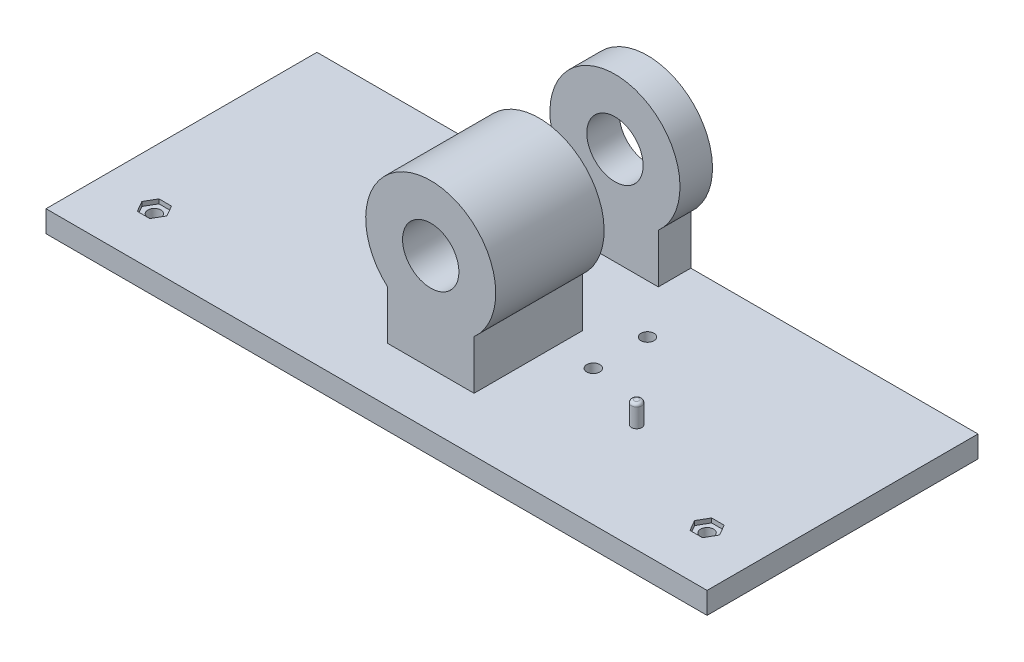
SolidWorks part; units mm, degrees
ref_plane "Front Plane" through (0, 0, 0) normal (0, 0, 1) x (1, 0, 0)
ref_plane "Top Plane" through (0, 0, 0) normal (0, 1, 0) x (1, 0, 0)
ref_plane "Right Plane" through (0, 0, 0) normal (1, 0, 0) x (0, 0, -1)
sketch "Sketch1" plane through (0, 0, 0) normal (0, 1, 0) x (1, 0, 0)
  line L0 (152.5, 125) -> (152.5, 0) construction
  line L1 (0, 0) -> (305, 0)
  line L2 (0, 0) -> (0, 125)
  line L3 (0, 125) -> (305, 125)
  line L4 (305, 0) -> (305, 125)
  line L5 (25, 100) -> (280, 100) construction
  line L6 (280, 25) -> (280, 100) construction
  line L7 (25, 25) -> (280, 25) construction
  line L8 (25, 25) -> (25, 100) construction
  line L9 (152.5, 62.5) -> (25, 62.5) construction
  line L10 (30.7735, 100) -> (27.8868, 105) construction
  line L11 (27.8868, 105) -> (22.1132, 105) construction
  line L12 (22.1132, 105) -> (19.2265, 100) construction
  line L13 (19.2265, 100) -> (22.1132, 95) construction
  line L14 (22.1132, 95) -> (27.8868, 95) construction
  line L15 (27.8868, 95) -> (30.7735, 100) construction
  line L16 (27.8868, 30) -> (30.7735, 25) construction
  line L17 (22.1132, 30) -> (27.8868, 30) construction
  line L18 (19.2265, 25) -> (22.1132, 30) construction
  line L19 (22.1132, 20) -> (19.2265, 25) construction
  line L20 (27.8868, 20) -> (22.1132, 20) construction
  line L21 (30.7735, 25) -> (27.8868, 20) construction
  line L22 (282.8868, 30) -> (277.1132, 30) construction
  line L23 (285.7735, 25) -> (282.8868, 30) construction
  line L24 (282.8868, 20) -> (285.7735, 25) construction
  line L25 (277.1132, 20) -> (282.8868, 20) construction
  line L26 (274.2265, 25) -> (277.1132, 20) construction
  line L27 (277.1132, 30) -> (274.2265, 25) construction
  line L28 (277.1132, 95) -> (274.2265, 100) construction
  line L29 (282.8868, 95) -> (277.1132, 95) construction
  line L30 (285.7735, 100) -> (282.8868, 95) construction
  line L31 (282.8868, 105) -> (285.7735, 100) construction
  line L32 (277.1132, 105) -> (282.8868, 105) construction
  line L33 (274.2265, 100) -> (277.1132, 105) construction
  line L34 (172.5, 75) -> (172.5, 125) construction
  line L35 (132.5, 0) -> (172.5, 0) construction
  line L36 (132.5, 0) -> (132.5, 125) construction
  line L37 (132.5, 125) -> (172.5, 125) construction
  line L38 (172.5, 0) -> (172.5, 125) construction
  line L39 (132.5, 75) -> (172.5, 75) construction
  line L40 (132.5, 75) -> (132.5, 25) construction
  line L41 (132.5, 25) -> (172.5, 25) construction
  line L42 (172.5, 75) -> (172.5, 25) construction
  line L43 (172.5, 75) -> (190, 62.5) construction
  line L48 (190, 62.5) -> (190, 75) construction
  line L49 (190, 75) -> (172.5, 75) construction
  line L50 (190, 62.5) -> (190, 75) construction
  line L51 (190, 75) -> (190, 87.5) construction
  circle A1 centre (25, 100) radius 5 construction
  circle A3 centre (280, 25) radius 3
  circle A4 centre (25, 25) radius 3
  circle A5 centre (190, 62.5) radius 3
  circle A7 centre (190, 87.5) radius 3
  dimension "D3" = 6
  dimension "D7" = 6
  dimension "D1" = 305
  dimension "D2" = 125
  dimension "D5" = 10
  dimension "D6" = 40
  dimension "D8" = 50
  dimension "D9" = 12.5
  dimension "D10" = 17.5
  dimension "D4" = 25
  dimension "D11" = 2
extrude "Boss-Extrude1" add sketch "Sketch1" along normal blind 10
sketch "Sketch6" plane through (0, 10, 0) normal (0, 1, 0) x (1, 0, 0)
  line L0 (152.5, 125) -> (152.5, 0) construction
  line L7 (305, 125) -> (0, 125) construction
  line L8 (0, 0) -> (305, 0) construction
  line L9 (152.5, 62.5) -> (0, 62.5) construction
  line L10 (0, 125) -> (0, 0) construction
  line L29 (27.8868, 30) -> (30.7735, 25)
  line L30 (274.2265, 25) -> (277.1132, 20)
  line L31 (277.1132, 20) -> (282.8868, 20)
  line L32 (282.8868, 20) -> (285.7735, 25)
  line L33 (285.7735, 25) -> (282.8868, 30)
  line L34 (282.8868, 30) -> (277.1132, 30)
  line L35 (277.1132, 30) -> (274.2265, 25)
  line L36 (22.1132, 30) -> (27.8868, 30)
  line L37 (19.2265, 25) -> (22.1132, 30)
  line L38 (22.1132, 20) -> (19.2265, 25)
  line L39 (27.8868, 20) -> (22.1132, 20)
  line L40 (30.7735, 25) -> (27.8868, 20)
  circle A0 centre (280, 25) radius 5 construction
  dimension "D1" = 10
extrude "Cut-Extrude1" cut sketch "Sketch6" against normal blind 2
sketch "Sketch7" plane through (0, 10, 0) normal (0, 1, 0) x (1, 0, 0)
  line L0 (0, 0) -> (305, 0) construction
  line L1 (132.5, 25) -> (172.5, 25)
  line L2 (132.5, 25) -> (132.5, 75)
  line L3 (132.5, 75) -> (172.5, 75)
  line L4 (172.5, 25) -> (172.5, 75)
  line L5 (152.5, 0) -> (152.5, 125) construction
  line L6 (305, 125) -> (0, 125) construction
  line L7 (172.5, 75) -> (172.5, 125) construction
  line L18 (132.5, 110) -> (172.5, 110)
  line L19 (132.5, 110) -> (132.5, 125)
  line L20 (132.5, 125) -> (172.5, 125)
  line L21 (172.5, 110) -> (172.5, 125)
  point P11 (152.5, 75)
  point P20 (152.5, 110)
  dimension "D1" = 40
  dimension "D4" = 15
extrude "Boss-Extrude2" add sketch "Sketch7" along normal blind 22.6393
sketch "Sketch11" plane through (0, 0, -25) normal (0, 0, 1) x (1, 0, 0)
  circle A0 centre (152.5, 55) radius 30
  circle A1 centre (152.5, 55) radius 13
  dimension "D1" = 60
  dimension "D2" = 26
extrude "Boss-Extrude3" add sketch "Sketch11" against normal up to surface (100 mm away) up to face at (152.5, 13.1598, -125)
ref_plane "Plane1" through (0, 0, -62.5) normal (0, 0, 1) x (1, 0, 0)
sketch "Sketch12" plane through (305, 0, 0) normal (1, 0, 0) x (0, 0, -1)
  line L0 (125, 85) -> (25, 85) construction
  line L1 (75, 10) -> (110, 10)
  line L2 (75, 10) -> (75, 85)
  line L3 (75, 85) -> (110, 85)
  line L4 (110, 10) -> (110, 85)
  line L6 (110, 32.6393) -> (110, 10) construction
extrude "Cut-Extrude2" cut sketch "Sketch12" against normal through all
sketch "Sketch13" plane through (0, 10, 0) normal (0, 1, 0) x (1, 0, 0)
  line L0 (222.5, 50) -> (172.5, 50) construction
  line L1 (172.5, 25) -> (172.5, 75) construction
  circle A1 centre (222.5, 50) radius 2.4
  dimension "D1" = 4.8
  dimension "D2" = 50
extrude "Boss-Extrude4" add sketch "Sketch13" along normal blind 10
sketch "Sketch14" plane through (0, 0, 0) normal (0, -1, 0) x (1, 0, 0)
  line L0 (195.7735, -87.5) -> (192.8868, -82.5)
  line L1 (195.7735, -62.5) -> (192.8868, -57.5)
  line L2 (192.8868, -57.5) -> (187.1132, -57.5)
  line L3 (187.1132, -57.5) -> (184.2265, -62.5)
  line L4 (184.2265, -62.5) -> (187.1132, -67.5)
  line L5 (187.1132, -67.5) -> (192.8868, -67.5)
  line L6 (192.8868, -67.5) -> (195.7735, -62.5)
  line L7 (192.8868, -82.5) -> (187.1132, -82.5)
  line L8 (187.1132, -82.5) -> (184.2265, -87.5)
  line L9 (184.2265, -87.5) -> (187.1132, -92.5)
  line L10 (187.1132, -92.5) -> (192.8868, -92.5)
  line L11 (192.8868, -92.5) -> (195.7735, -87.5)
  circle A0 centre (190, -62.5) radius 5 construction
  dimension "D1" = 10
  dimension "D3" = 15
  dimension "D2" = 2
extrude "Cut-Extrude3" cut sketch "Sketch14" against normal blind 4
fillet "Fillet1" radius 1.3 1 edges at (222.5, 20, -47.6)
equation "\"joint_width\"=4"
equation "\"D2@Sketch7\"=5"
equation "\"short_base_length\"=12.5"
equation "\"D2@Sketch1\"=\"short_base_length\""
equation "\"outer_diam_main_joint\"=6"
equation "\"D1@Sketch11\"=\"outer_diam_main_joint\""
equation "\"D1@Sketch7\"=\"outer_diam_main_joint\"-2"
equation "\"D1@Boss-Extrude2\"=(\"outer_diam_main_joint\"/2)+1.5cm-sqr((\"outer_diam_main_joint\"/2)^2-((\"outer_diam_main_joint\"-2)/2)^2)"
equation "\"D6@Sketch1\"=\"outer_diam_main_joint\"-2"
equation "\"pulleyside\"=1.5"
